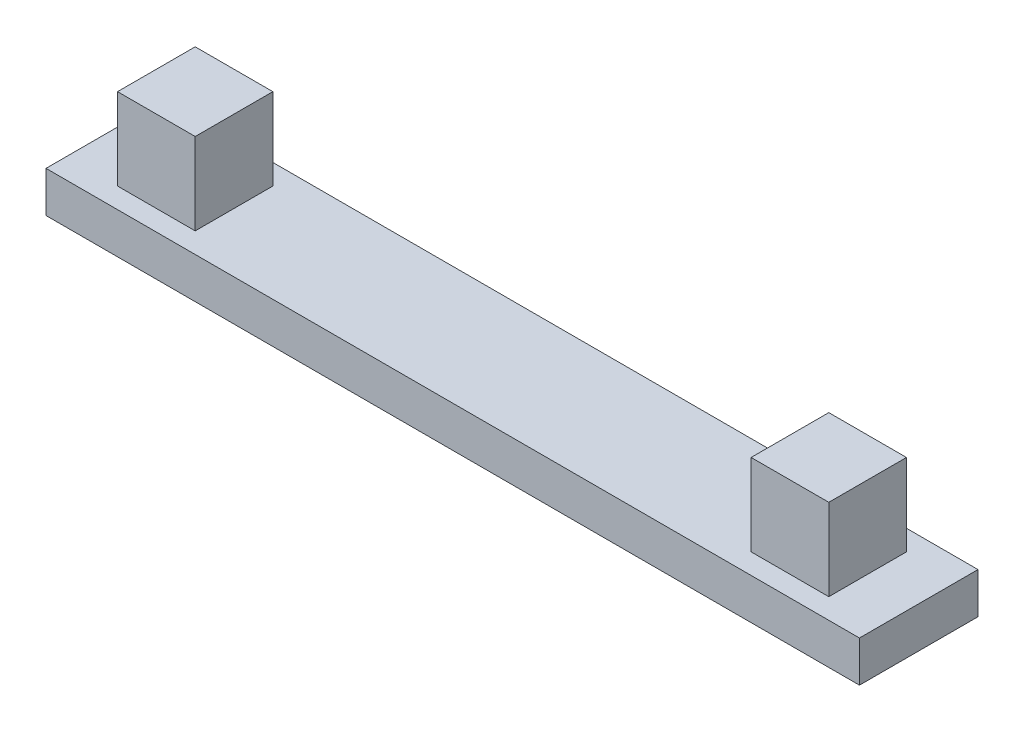
SolidWorks part; units mm, degrees
ref_plane "Front Plane" through (0, 0, 0) normal (0, 0, 1) x (1, 0, 0)
ref_plane "Top Plane" through (0, 0, 0) normal (0, 1, 0) x (1, 0, 0)
ref_plane "Right Plane" through (0, 0, 0) normal (1, 0, 0) x (0, 0, -1)
sketch "Sketch1" plane through (0, 0, 0) normal (0, 1, 0) x (1, 0, 0)
  line L1 (0, 0) -> (19.9, 0)
  line L2 (0, 0) -> (0, 2.9)
  line L3 (0, 2.9) -> (19.9, 2.9)
  line L4 (19.9, 0) -> (19.9, 2.9)
  line L5 (0, 0) -> (19.9, 2.9) construction
  line L6 (0, 2.9) -> (19.9, 0) construction
  line L7 (1.25, 2.4) -> (3.15, 2.4)
  line L8 (1.25, 2.4) -> (1.25, 0.5)
  line L9 (1.25, 0.5) -> (3.15, 0.5)
  line L10 (3.15, 2.4) -> (3.15, 0.5)
  line L11 (1.25, 2.4) -> (3.15, 0.5) construction
  line L12 (1.25, 0.5) -> (3.15, 2.4) construction
  line L13 (16.75, 2.4) -> (18.65, 2.4)
  line L14 (16.75, 2.4) -> (16.75, 0.5)
  line L15 (16.75, 0.5) -> (18.65, 0.5)
  line L16 (18.65, 2.4) -> (18.65, 0.5)
  line L17 (16.75, 2.4) -> (18.65, 0.5) construction
  line L18 (16.75, 0.5) -> (18.65, 2.4) construction
  point P4 (9.95, 1.45)
  point P10 (2.2, 1.45)
  point P15 (17.7, 1.45)
  point P17 (0, 1.45)
  point P22 (19.9, 1.45)
  dimension "D1" = 19.9
  dimension "D2" = 2.9
  dimension "D3" = 15.5
  dimension "D4" = 1.9
  dimension "D5" = 7.75
extrude "Boss-Extrude1" add sketch "Sketch1" along normal blind 1 contours L1 L4 L3 L2 L7 L10 L9 L8 L13 L16 L15 L14 region at (9.95, 0, -1.45)
ref_plane "Plane1" through (3.15, 0, -2.4) normal (1, 0, 0) x (0, 0, -1)
extrude "Boss-Extrude2" add sketch "Sketch1<3>" along normal blind 3 contours L7 L10 L9 L8 | L13 L16 L15 L14
sketch "Sketch1<3>" plane through (0, 0, 0) normal (0, 1, 0) x (1, 0, 0) same geometry as "Sketch1"
